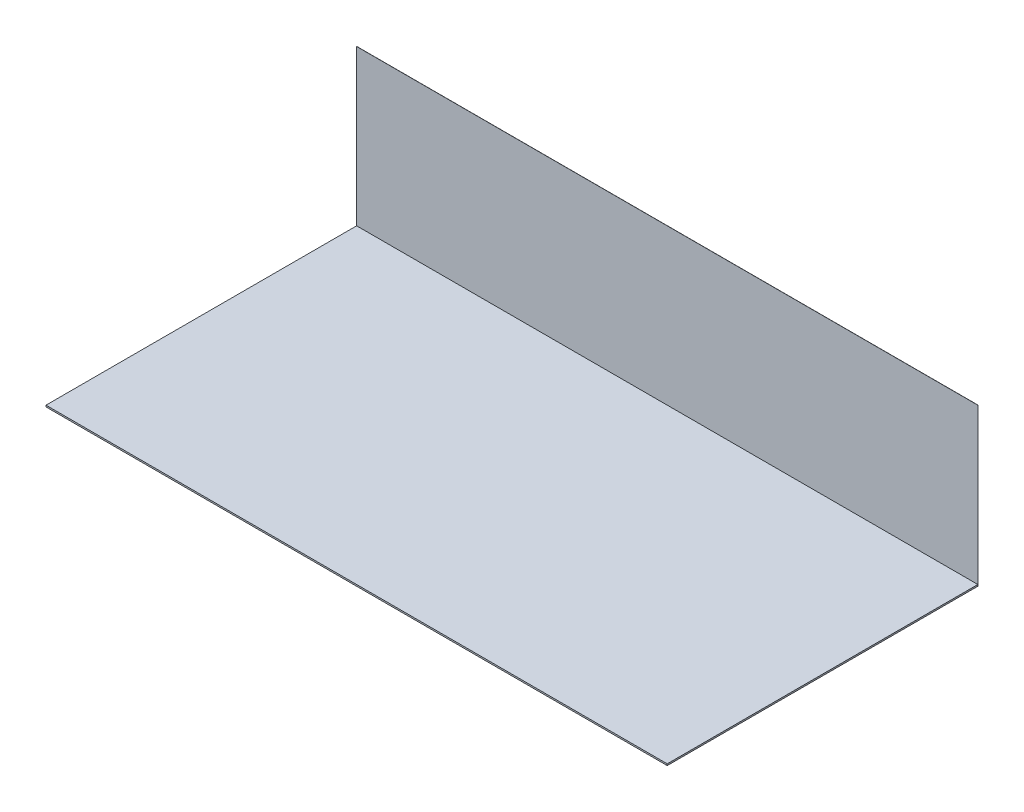
SolidWorks part; units mm, degrees
other "Floor"
ref_plane "Front Plane" through (0, 0, 0) normal (0, 0, 1) x (1, 0, 0)
ref_plane "Top Plane" through (0, 0, 0) normal (0, 1, 0) x (1, 0, 0)
ref_plane "Right Plane" through (0, 0, 0) normal (1, 0, 0) x (0, 0, -1)
sketch "Sketch2" plane through (0, 0, 0) normal (0, 1, 0) x (1, 0, 0)
  line L1 (-83.0204, 20.3435) -> (18.5796, 20.3435)
  line L2 (-83.0204, 20.3435) -> (-83.0204, -30.4565)
  line L3 (-83.0204, -30.4565) -> (18.5796, -30.4565)
  line L4 (18.5796, 20.3435) -> (18.5796, -30.4565)
  dimension "Width_Floor" = 50.8
  dimension "Length_Floor" = 101.6
extrude "Floor" add sketch "Sketch2" along normal blind 0.254
sketch "Sketch4" plane through (0, 0.254, 0) normal (0, 1, 0) x (1, 0, 0)
  line L0 (18.5796, 20.3435) -> (-83.0204, 20.3435) construction
  line L1 (18.5796, 20.3435) -> (-83.0204, 20.3435)
extrude "Wall1" add sketch "Sketch4" along normal blind 25.4 separate body thin thin type one direction wall 0.0254
